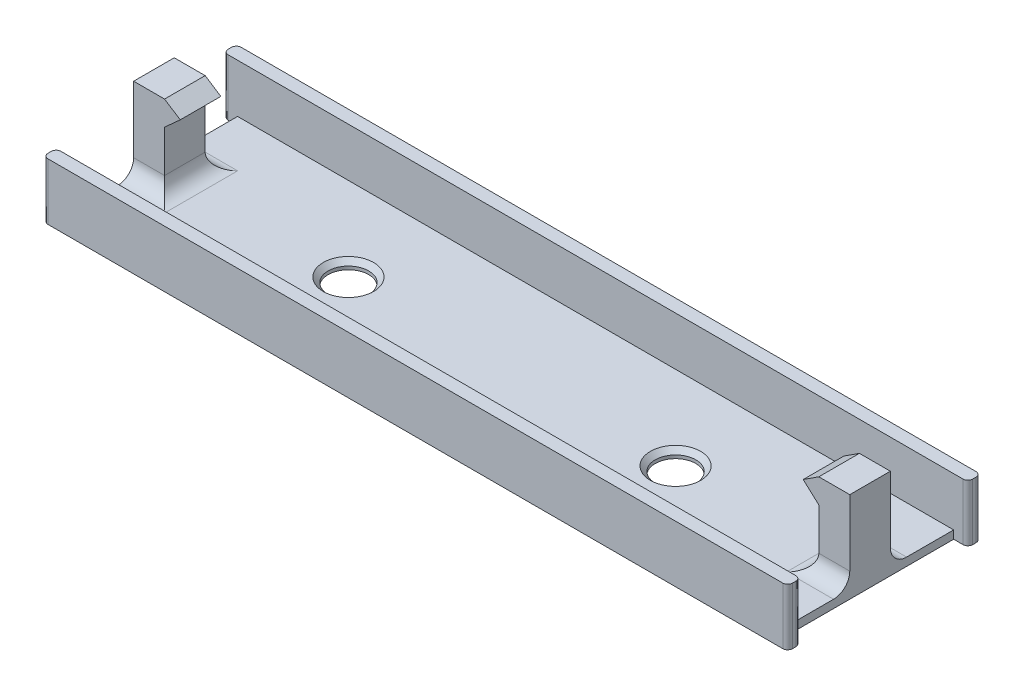
SolidWorks part; units mm, degrees
ref_plane "Front Plane" through (0, 0, 0) normal (0, 0, 1) x (1, 0, 0)
ref_plane "Top Plane" through (0, 0, 0) normal (0, 1, 0) x (1, 0, 0)
ref_plane "Right Plane" through (0, 0, 0) normal (1, 0, 0) x (0, 0, -1)
sketch "Sketch1" plane through (0, 0, 0) normal (0, 1, 0) x (1, 0, 0)
  line L1 (0, 0) -> (80.6, 0)
  line L2 (0, 0) -> (0, 20.6)
  line L3 (0, 20.6) -> (80.6, 20.6)
  line L4 (80.6, 0) -> (80.6, 20.6)
  line L8 (40.3, 20.6) -> (40.3, 0) construction
  line L13 (40.3, 10.3) -> (80.6, 10.3) construction
  line L14 (80.6, 12.8) -> (84.41, 12.8)
  line L15 (80.6, 7.8) -> (84.41, 7.8)
  line L16 (84.41, 0) -> (84.41, 20.6)
  line L17 (86.16, 0) -> (-5.56, 0)
  line L18 (0, 7.8) -> (-3.81, 7.8)
  line L19 (0, 12.8) -> (-3.81, 12.8)
  line L20 (86.16, 0) -> (86.16, -1.6)
  line L21 (86.16, -1.6) -> (-5.56, -1.6)
  line L22 (-5.56, 0) -> (-5.56, -1.6)
  line L27 (-3.81, 0) -> (-3.81, 20.6)
  line L28 (-5.56, 20.6) -> (-5.56, 22.2)
  line L29 (86.16, 22.2) -> (-5.56, 22.2)
  line L30 (86.16, 20.6) -> (86.16, 22.2)
  line L31 (86.16, 20.6) -> (-5.56, 20.6)
  circle A0 centre (60.45, 10.3) radius 2.5
  circle A1 centre (20.15, 10.3) radius 2.5
  dimension "D7" = 5
  dimension "D1" = 20.6
  dimension "D2" = 80.6
  dimension "D4" = 1.6
  dimension "D5" = 5
  dimension "D6" = 1.75
  dimension "D3" = 3.81
  dimension "D8" = 91.72
extrude "Boss-Extrude1" add sketch "Sketch1" against normal blind 1 contours L22 | L19 L2 L3 | L2 L19 L18 | L1 L2 L18 | L1 L4 L3 L2 A0 A1 | L3 | L1 | L15 L4 L1 | L3 L4 L14 | L4 L15 L14 | L22 | L22 region at (40.3, 0, -10.3) region at (-1.905, 0, -3.9) region at (40.3, 0, 0.8) region at (82.505, 0, -3.9) region at (-1.905, 0, -10.3) region at (82.505, 0, -10.3) region at (-1.905, 0, -16.7) region at (82.505, 0, -16.7) region at (40.3, 0, -21.4)
extrude "Boss-Extrude2" add sketch "Sketch1<3>" along normal blind 10.16 contours L2 L19 L18 | L4 L15 L14 region at (-1.905, 0, -10.3) region at (82.505, 0, -10.3)
sketch "Sketch1<3>" plane through (0, 0, 0) normal (0, 1, 0) x (1, 0, 0) same geometry as "Sketch1"
extrude "Boss-Extrude3" add sketch "Sketch1<4>" along normal blind 6 contours L1 | L3 region at (40.3, 0, 0.8) region at (40.3, 0, -21.4)
sketch "Sketch1<4>" plane through (0, 0, 0) normal (0, 1, 0) x (1, 0, 0) same geometry as "Sketch1"
sketch "Sketch2" plane through (0, 0, -7.8) normal (0, 0, 1) x (1, 0, 0)
  line L0 (0, 10.16) -> (1.9274, 8.905)
  line L1 (1.9274, 8.905) -> (0, 7.16)
  line L2 (0, 10.16) -> (0, 0) construction
  line L3 (0, 7.16) -> (0, 10.16)
  dimension "D1" = 2.3
  dimension "D2" = 2.6
  dimension "D3" = 3
extrude "Boss-Extrude4" add sketch "Sketch2" against normal up to surface (5 mm away) up to face at (-1.905, 5.08, -12.8)
ref_plane "Plane1" through (40.3, 0, 0) normal (1, 0, 0) x (0, 0, -1)
mirror "Mirror1" about plane through (40.3, 0, 0) normal (1, 0, 0) of "Boss-Extrude4"
fillet "Fillet2" radius 2 6 edges at (80.6, 0, -10.3) (0, 0, -10.3) (82.505, 0, -12.8) (82.505, 0, -7.8) (-1.905, 0, -12.8) (-1.905, 0, -7.8)
chamfer "Chamfer1" distance 0.6 angle 45 2 edges at (60.45, 0, -7.8) (20.15, 0, -7.8)
fillet "Fillet3" radius 0.6 8 edges at (-5.56, 2.5, 1.6) (-5.56, 2.5, 0) (-5.56, 2.5, -20.6) (-5.56, 2.5, -22.2) (86.16, 2.5, -22.2) (86.16, 2.5, -20.6) (86.16, 2.5, 1.6) (86.16, 2.5, 0)
